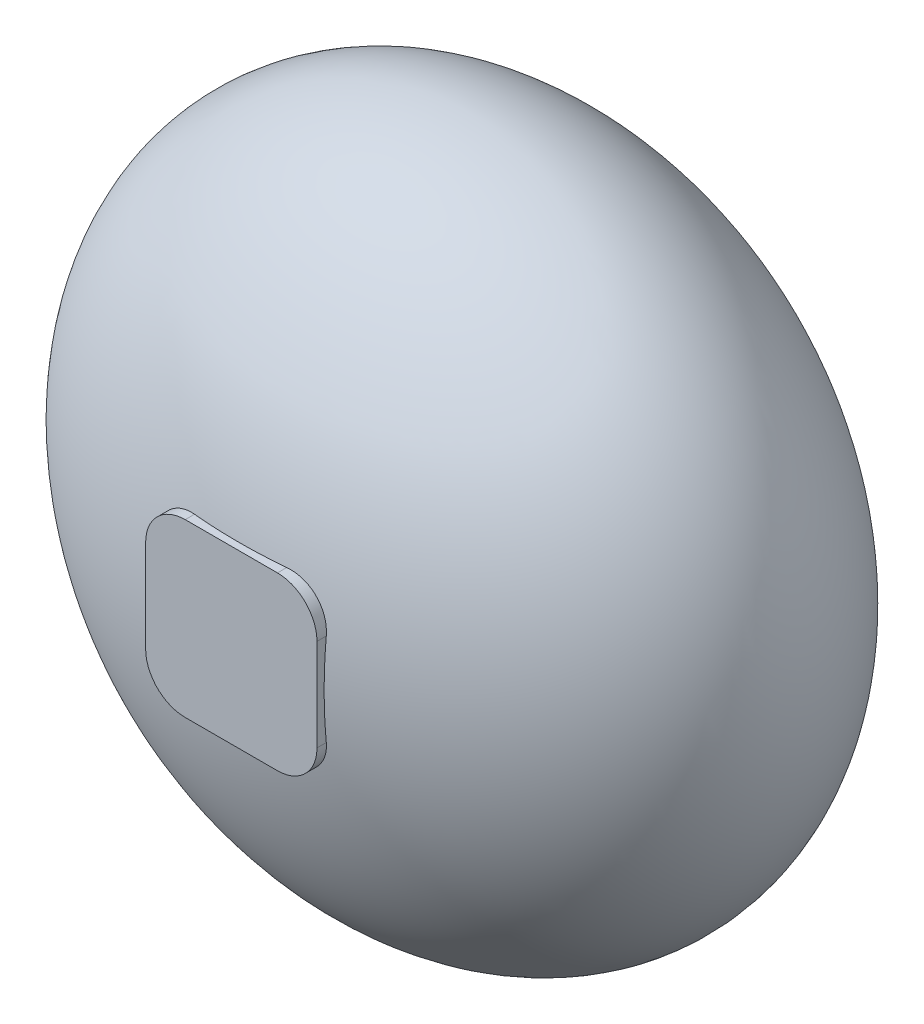
SolidWorks part; units mm, degrees
ref_plane "Front Plane" through (0, 0, 0) normal (0, 0, 1) x (1, 0, 0)
ref_plane "Top Plane" through (0, 0, 0) normal (0, 1, 0) x (1, 0, 0)
ref_plane "Right Plane" through (0, 0, 0) normal (1, 0, 0) x (0, 0, -1)
other "Center of Mass"
sketch "Sketch1" plane through (0, 0, 0) normal (0, 1, 0) x (1, 0, 0)
  line L0 (0, 17.5) -> (0, -17.5) construction
  line L1 (0, 17.5) -> (0, -17.5)
  ellipse E0 centre (0, 0) end of major axis (-26.25, 0) minor radius 17.5 (0, -17.5) -> (0, 17.5) ccw
  dimension "D1" = 17.5
  dimension "D2" = 26.25
revolve "Revolve4" add sketch "Sketch1" angle 360 about L0
sketch "Sketch2" plane through (0, 0, 0) normal (0, 0, 1) x (1, 0, 0)
  line L1 (6.5, -6.5) -> (-6.5, -6.5)
  line L2 (6.5, -6.5) -> (6.5, 6.5)
  line L3 (6.5, 6.5) -> (-6.5, 6.5)
  line L4 (-6.5, -6.5) -> (-6.5, 6.5)
  line L5 (6.5, -6.5) -> (-6.5, 6.5) construction
  line L6 (6.5, 6.5) -> (-6.5, -6.5) construction
  point P0 (0, 0)
  dimension "D1" = 13
extrude "Boss-Extrude1" add sketch "Sketch2" along normal through all
fillet "Fillet1" radius 3 4 edges at (6.5, -6.5, 16.946) (-6.5, 6.5, 16.946) (6.5, 6.5, 16.946) (-6.5, -6.5, 16.946)
sketch "Sketch3" plane through (0, 0, 0) normal (0, 0, 1) x (1, 0, 0)
  circle A0 centre (0, 0) radius 7
  dimension "D1" = 14
extrude "Cut-Extrude1" cut sketch "Sketch3" along normal blind 13
